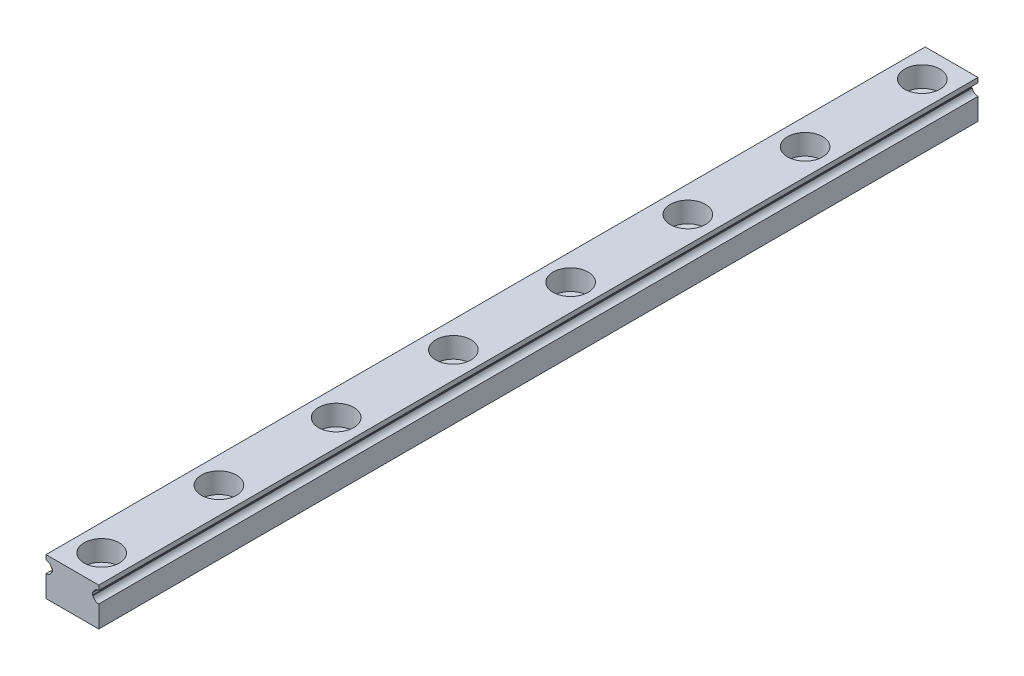
SolidWorks part; units mm, degrees
material "6061 合金"
ref_plane "Спереди" through (0, 0, 0) normal (0, 0, 1) x (1, 0, 0)
ref_plane "Сверху" through (0, 0, 0) normal (0, 1, 0) x (1, 0, 0)
ref_plane "Справа" through (0, 0, 0) normal (1, 0, 0) x (0, 0, -1)
sketch "Sketch1" plane through (0, 0, 0) normal (0, 0, 1) x (1, 0, 0)
  line L0 (0, 0) -> (0, 5.7299) construction
  line L1 (-4.5, -3.25) -> (4.5, -3.25)
  line L2 (-4.5, -3.25) -> (-4.5, 0.45)
  line L3 (-4.5, 3.25) -> (4.5, 3.25)
  line L4 (4.5, -3.25) -> (4.5, 0.45)
  line L5 (-4.5, -3.25) -> (4.5, 3.25) construction
  line L6 (-4.5, 3.25) -> (4.5, -3.25) construction
  line L7 (-4.5, 2.45) -> (-4.5, 3.25)
  line L8 (-3.5318, 1.2) -> (-3.4, 1.2)
  line L9 (3.5318, 1.2) -> (3.4, 1.2)
  line L10 (-3.5318, 1.7) -> (-3.4, 1.7)
  line L11 (-3.4, 1.2) -> (-3.4, 1.7)
  line L12 (3.4, 1.2) -> (3.4, 1.7)
  line L13 (3.5318, 1.7) -> (3.4, 1.7)
  line L14 (4.5, 2.45) -> (4.5, 3.25)
  line L15 (-3.4, 1.45) -> (-4.5, 1.45) construction
  arc A0 (-3.5318, 1.7) -> (-4.5, 2.45) centre (-4.5, 1.45) ccw
  arc A1 (-4.5, 0.45) -> (-3.5318, 1.2) centre (-4.5, 1.45) ccw
  arc A2 (4.5, 0.45) -> (3.5318, 1.2) centre (4.5, 1.45) cw
  arc A3 (3.5318, 1.7) -> (4.5, 2.45) centre (4.5, 1.45) cw
  point P0 (0, 0)
  dimension "D3" = 1
  dimension "D1" = 9
  dimension "D2" = 6.5
  dimension "D4" = 2.05
  dimension "D5" = 6.8
  dimension "D6" = 0.5
extrude "Extrude1" add sketch "Sketch1" along normal blind 150
sketch "Sketch2" plane through (0, 3.25, 0) normal (0, 1, 0) x (1, 0, 0)
  line L0 (4.5, 0) -> (-4.5, 0) construction
  circle A0 centre (0, -5) radius 1.75
  circle A1 centre (0, -5) radius 3
  dimension "D1" = 3.5
  dimension "D2" = 6
  dimension "D3" = 5
extrude "Extrude2" cut sketch "Sketch2" against normal blind 3.5 contours A1
extrude "Extrude3" cut sketch "Sketch" against normal through all contours A0
sketch "Sketch" plane through (0, 3.25, 0) normal (0, 1, 0) x (1, 0, 0) same geometry as "Sketch2"
pattern_linear "LPattern1" count 40 spacing 20 along (0, 0, 1) of "Extrude2", "Extrude3"
chamfer "Chamfer1" [suppressed] distance 0.3 angle 45
sketch "草图1" plane through (0, 3.25, 0) normal (0, 1, 0) x (1, 0, 0)
  line L1 (4.5, -150) -> (4.5, 0) construction
  point P0 (0, -75)
  point P5 (4.5, -75)
ref_plane "基准面1" through (0, 0, 0) normal (0, 1, 0) x (1, 0, 0)
sketch "草图3" plane through (0, 0, 0) normal (0, 1, 0) x (1, 0, 0)
  line L0 (0, -150) -> (0, 0) construction
  line L1 (4.5, -150) -> (-4.5, -150) construction
  line L2 (4.5, 0) -> (-4.5, 0) construction
  point P6 (0, -75)
  point P7 (0, -75)
